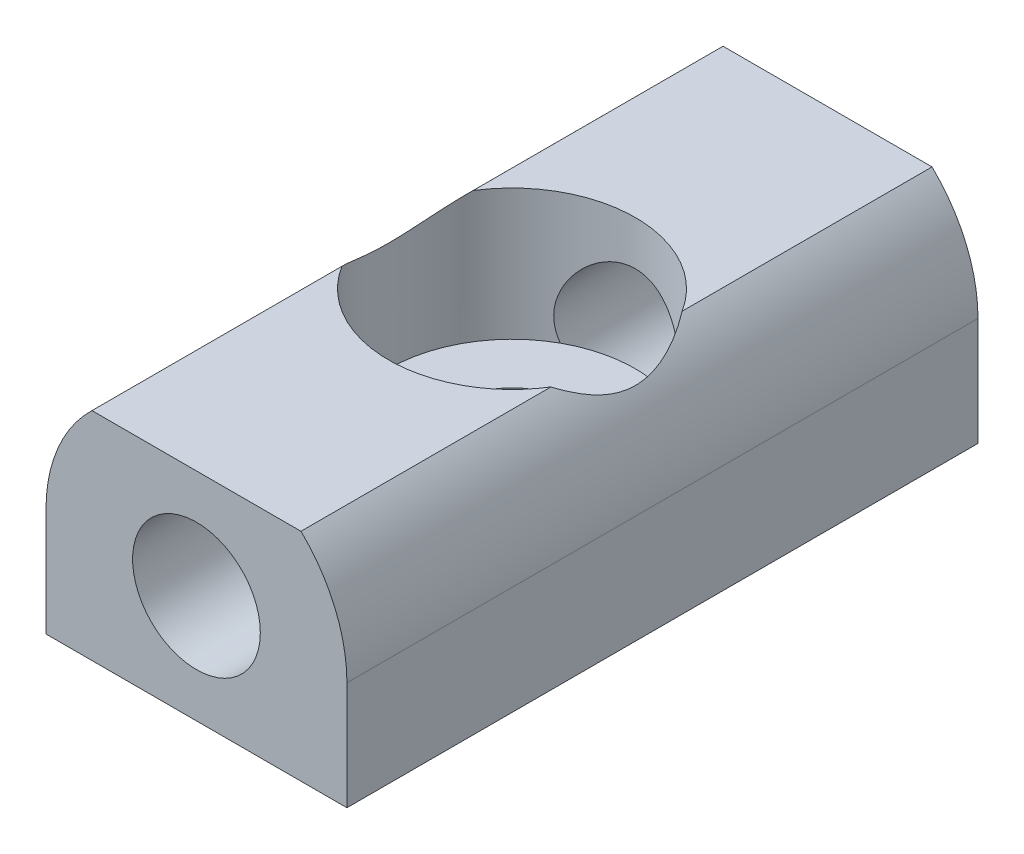
SolidWorks part; units mm, degrees
ref_plane "Front Plane" through (0, 0, 0) normal (0, 0, 1) x (1, 0, 0)
ref_plane "Top Plane" through (0, 0, 0) normal (0, 1, 0) x (1, 0, 0)
ref_plane "Right Plane" through (0, 0, 0) normal (1, 0, 0) x (0, 0, -1)
sketch "Sketch2" plane through (0, 0, 0) normal (0, 0, 1) x (1, 0, 0)
  circle A0 centre (0, 0) radius 1.475
  circle A1 centre (0, 0) radius 3.475
  dimension "D1" = 2.95
  dimension "D2" = 2
extrude "Boss-Extrude2" add sketch "Sketch2" along normal blind 14.575 contours A1
sketch "Sketch3" plane through (0, 0, 14.575) normal (0, 0, 1) x (1, 0, 0)
  circle A0 centre (0, 0) radius 1.475
  dimension "D1" = 2.95
extrude "Cut-Extrude1" cut sketch "Sketch3" against normal blind 10
sketch "Sketch4" plane through (0, 0, 0) normal (0, 0, -1) x (-1, 0, 0)
  circle A0 centre (0, 0) radius 1.475
  dimension "D1" = 2.95
extrude "Cut-Extrude2" cut sketch "Sketch4" against normal blind 10
sketch "Sketch5" plane through (0, 0, 0) normal (0, 0, -1) x (-1, 0, 0)
  line L0 (3.475, 0) -> (3.475, 1.469)
  line L2 (-3.475, 0) -> (3.475, 0)
  line L3 (-3.475, 0) -> (-3.475, -3.475)
  line L4 (-3.475, -3.475) -> (3.475, -3.475)
  line L5 (3.475, 0) -> (3.475, -3.475)
  circle A0 centre (0, 0) radius 3.475
  circle M7 centre (0, 0) radius 3.475
extrude "Boss-Extrude3" add sketch "Sketch5" against normal up to surface (14.575 mm away) contours L3 L4 M7 | L5 L4 M7 region at (2.6988, -2.6988, 0) region at (-2.6988, -2.6988, 0) up to face at (1.475, 0, 14.575)
sketch "Sketch6" plane through (0, -3.475, 0) normal (0, -1, 0) x (1, 0, 0)
  line L1 (-3.475, 14.575) -> (3.475, 14.575)
  line L2 (-3.475, 14.575) -> (-3.475, 0)
  line L3 (-3.475, 0) -> (3.475, 0)
  line L4 (3.475, 14.575) -> (3.475, 0)
extrude "Boss-Extrude4" add sketch "Sketch6" along normal blind 0.2
sketch "Sketch8" plane through (-3.475, 0, 0) normal (-1, 0, 0) x (0, 0, 1)
  line L0 (7.2875, -3.675) -> (15.3423, 7.0199)
  line L1 (14.575, -3.675) -> (0, -3.675) construction
  line L2 (14.575, 3.475) -> (0, 3.475) construction
  line L3 (4.2875, 2.475) -> (10.2875, 2.475)
  line L4 (4.2875, 2.475) -> (4.2875, 4.475)
  line L5 (4.2875, 4.475) -> (10.2875, 4.475)
  line L6 (10.2875, 2.475) -> (10.2875, 4.475)
  line L7 (4.2875, 2.475) -> (10.2875, 4.475) construction
  line L8 (4.2875, 4.475) -> (10.2875, 2.475) construction
  point P4 (7.2875, 3.475)
  dimension "D1" = 6
  dimension "D2" = 2
extrude "Cut-Extrude3" cut sketch "Sketch8" against normal through all contours L3 L6 L5 L4 region at (-3.475, 3.475, 7.2875)
sketch "Sketch10" plane through (0, 2.475, 0) normal (0, 1, 0) x (1, 0, 0)
  line L0 (-2.4393, -4.2875) -> (2.4393, -10.2875)
  circle A0 centre (0, -7.2875) radius 2.85
  line M2 (2.4393, -10.2875) -> (2.4393, -4.2875)
  line M4 (-2.4393, -4.2875) -> (-2.4393, -10.2875)
  dimension "D1" = 5.7
extrude "Cut-Extrude4" cut sketch "Sketch10" against normal blind 3 contours L0 A0 M2 | A0 M2 | L0 A0 M4 | A0 M4 | A0 region at (0.8241, 2.475, 6.472) region at (-0.8241, 2.475, 8.103) region at (-2.6046, 2.475, 7.2875) region at (2.6046, 2.475, 7.2875)
sketch "Sketch11" plane through (0, -0.525, 0) normal (0, 1, 0) x (1, 0, 0)
  circle A0 centre (0, -7.2875) radius 1.675
  dimension "D1" = 3.35
extrude "Cut-Extrude5" cut sketch "Sketch11" against normal through all
sketch "Sketch17" plane through (0, -0.525, 0) normal (0, 1, 0) x (1, 0, 0)
  circle A0 centre (0, -7.2875) radius 1.675
  circle A1 centre (0, -7.2875) radius 2.85
extrude "Boss-Extrude8" add sketch "Sketch17" against normal up to surface (3.15 mm away) contours A1 up to face at (0, -3.675, 8.9625)
sketch "Sketch18" plane through (0, 0, 4.2875) normal (0, 0, 1) x (1, 0, 0)
  line L0 (2.4393, 2.475) -> (-2.4393, 2.475)
  circle A0 centre (0, 0) radius 3.475
  arc M1 (2.4393, 2.475) -> (-2.4393, 2.475) centre (0, 0) ccw
  line M2 (-2.4393, 2.475) -> (2.4393, 2.475)
extrude "Boss-Extrude9" add sketch "Sketch18" along normal up to surface (1.5261 mm away) contours M2 M1 region at (0, 2.8804, 4.2875) up to face at (0, 0.4742, 7.2875)
sketch "Sketch20" plane through (0, 2.475, 0) normal (0, 1, 0) x (1, 0, 0)
  line L0 (-2.4393, -8.7614) -> (-2.4393, -10.2875)
  line L1 (-2.4393, -10.2875) -> (2.4393, -10.2875)
  line L2 (2.4393, -10.2875) -> (2.4393, -8.7614)
  circle A0 centre (0, -7.2875) radius 2.85
  line M2 (2.4393, -10.2875) -> (2.4393, -8.7614)
  arc M3 (2.4393, -8.7614) -> (-2.4393, -8.7614) centre (0, -7.2875) cw
  line M4 (-2.4393, -8.7614) -> (-2.4393, -10.2875)
  line M5 (-2.4393, -10.2875) -> (2.4393, -10.2875)
extrude "Boss-Extrude12" add sketch "Sketch20" along normal blind 4 contours M5 M2 M3 M4 region at (0, 2.475, 10.1886)
sketch "Sketch21" plane through (0, 0, 14.575) normal (0, 0, 1) x (1, 0, 0)
  line L0 (-2.7993, 2.059) -> (-2.996, 6.8101)
  line L1 (-2.996, 6.8101) -> (3.8257, 6.9138)
  line L2 (3.8257, 6.9138) -> (2.6196, 2.2833)
  circle A0 centre (0, 0) radius 3.475
  arc M2 (3.475, 0) -> (-3.475, 0) centre (0, 0) ccw
extrude "Cut-Extrude6" cut sketch "Sketch21" against normal through all contours L2 L1 L0 M2 region at (0.2103, 5.0021, 14.575)
sketch "Sketch23" plane through (0, -0.525, 0) normal (0, 1, 0) x (1, 0, 0)
  circle A0 centre (0, -7.2875) radius 1.475
  dimension "D1" = 2.95
extrude "Cut-Extrude8" cut sketch "Sketch23" against normal through all
sketch "Sketch24" plane through (0, 0, 14.575) normal (0, 0, 1) x (1, 0, 0)
  line L1 (-5.5197, -2.5) -> (5.5197, -2.5)
  line L2 (-5.5197, -2.5) -> (-5.5197, 2.5)
  line L3 (-5.5197, 2.5) -> (5.5197, 2.5)
  line L4 (5.5197, -2.5) -> (5.5197, 2.5)
  line L5 (-5.5197, -2.5) -> (5.5197, 2.5) construction
  line L6 (-5.5197, 2.5) -> (5.5197, -2.5) construction
  line L7 (-3.7664, -3.8734) -> (3.7664, -3.8734)
  line L8 (-3.7664, -3.8734) -> (-3.7664, 3.8734)
  line L9 (-3.7664, 3.8734) -> (3.7664, 3.8734)
  line L10 (3.7664, -3.8734) -> (3.7664, 3.8734)
  line L11 (-3.7664, -3.8734) -> (3.7664, 3.8734) construction
  line L12 (-3.7664, 3.8734) -> (3.7664, -3.8734) construction
  point P0 (0, 0)
  point P6 (0, 0)
  arc M3 (3.475, 0) -> (-3.475, 0) centre (0, 0) ccw
  line M4 (-3.475, 0) -> (-3.475, -3.675)
  line M5 (-3.475, -3.675) -> (3.475, -3.675)
  line M6 (3.475, -3.675) -> (3.475, 0)
  dimension "D1" = 5
extrude "Cut-Extrude9" cut sketch "Sketch24" against normal through all contours L3 M3 | L1 M4 M5 M6 region at (0, -3.0875, 14.575) region at (0, 2.8951, 14.575)
